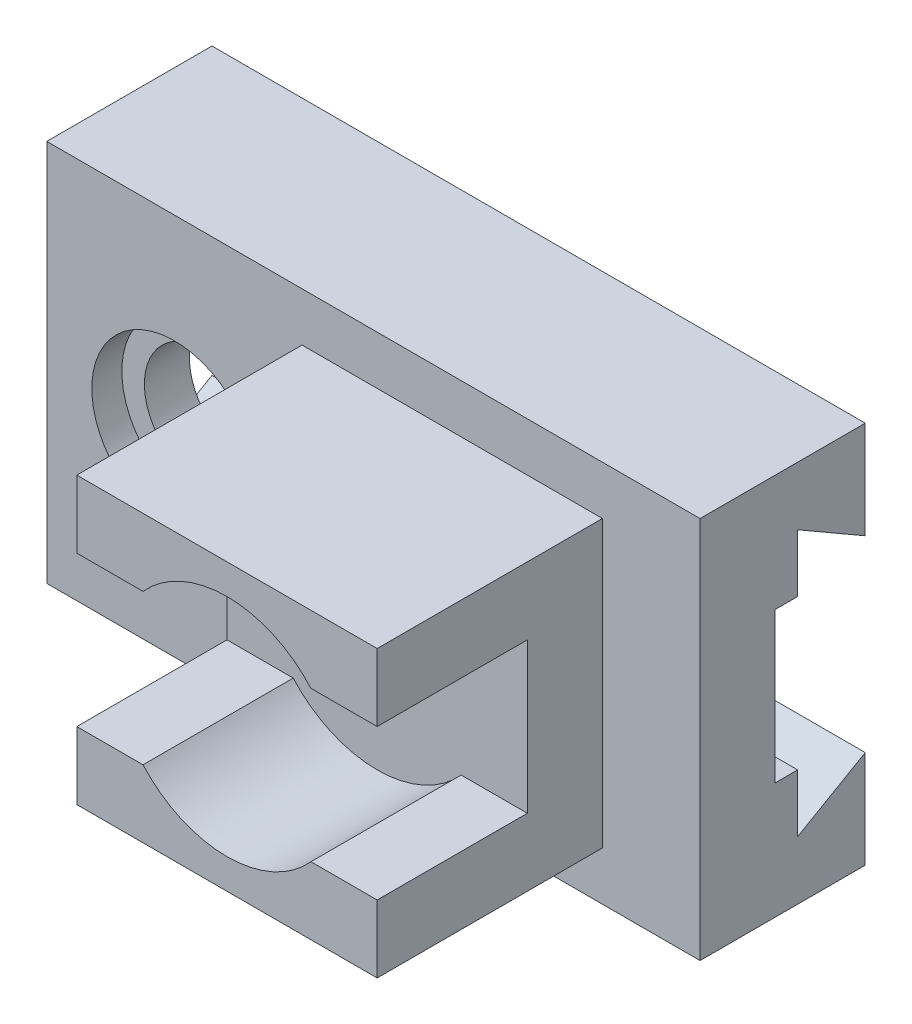
SolidWorks part; units mm, degrees
ref_plane "Front Plane" through (0, 0, 0) normal (0, 0, 1) x (1, 0, 0)
ref_plane "Top Plane" through (0, 0, 0) normal (0, 1, 0) x (1, 0, 0)
ref_plane "Right Plane" through (0, 0, 0) normal (1, 0, 0) x (0, 0, -1)
sketch "Sketch1" plane through (0, 0, 0) normal (0, 0, 1) x (1, 0, 0)
  line L0 (0, 29.2968) -> (0, -38.6677) construction
  line L1 (-48.5899, 0) -> (49.2377, 0) construction
  line L2 (-43.5, 25.491) -> (-43.5, -25.491)
  line L3 (-43.5, -25.491) -> (43.5, -25.491)
  line L4 (43.5, -25.491) -> (43.5, 25.491)
  line L5 (43.5, 25.491) -> (-43.5, 25.491)
  dimension "lengthbox" = 87
  dimension "highbox" = 50.982
extrude "base-yellow" add sketch "Sketch1" against normal blind 22
sketch "Sketch2" plane through (0, 0, 0) normal (0, 0, 1) x (1, 0, 0)
  line L0 (-55.6023, 0) -> (42.5138, 0) construction
  line L1 (-26.5, 34.8231) -> (-26.5, -37.4981) construction
  line L2 (0, 34.1505) -> (0, -37.5061) construction
  line L4 (-43.5, 25.491) -> (-43.5, -25.491) construction
  circle A0 centre (-26.5, 0) radius 11
  circle A1 centre (-26.5, 0) radius 8
  dimension "D1" = 22
  dimension "D2" = 16
  dimension "half dist" = 17
extrude "counterbor" cut sketch "Sketch2" against normal blind 4 contours A0
extrude "counterbor2" cut sketch "Sketch2<5>" against normal through all contours A1 region at (-26.5, 0, 0)
sketch "Sketch2<5>" plane through (0, 0, 0) normal (0, 0, 1) x (1, 0, 0) same geometry as "Sketch2"
ref_plane "Plane1" through (0, 0, 0) normal (0, 0, 1) x (1, 0, 0)
sketch "Sketch5" plane through (0, 0, 0) normal (0, 0, 1) x (1, 0, 0)
  line L0 (-58.6404, 0) -> (51.5993, 0) construction
  line L1 (0, 33.7865) -> (0, -36.0985) construction
  line L2 (-9.5, 19) -> (-9.5, -19)
  line L3 (-9.5, -19) -> (30.5, -19)
  line L4 (30.5, -19) -> (30.5, 19)
  line L5 (30.5, 19) -> (-9.5, 19)
  line L6 (-43.5, 25.491) -> (-43.5, -25.491) construction
  dimension "D1" = 38
  dimension "D2" = 40
  dimension "dist" = 34
extrude "base-red" add sketch "Sketch5" along normal blind 30
sketch "Sketch7" plane through (0, 0, 30) normal (0, 0, 1) x (1, 0, 0)
  line L0 (0, 34.1018) -> (0, -39.0411) construction
  line L1 (52.8604, 0) -> (-64.4204, 0) construction
  line L2 (10.5, 16.6451) -> (10.5, -21.924) construction
  line L10 (-9.5, 19) -> (-9.5, -19) construction
  line L11 (-9.5, -10) -> (30.5, -10)
  line L12 (-9.5, -10) -> (-9.5, 10)
  line L13 (-9.5, 10) -> (30.5, 10)
  line L14 (30.5, -10) -> (30.5, 10)
  line L15 (30.5, -19) -> (30.5, 19) construction
  circle A0 centre (10.5, 0) radius 15
  dimension "D2" = 30
  dimension "D1" = 20
extrude "base-purple" cut sketch "Sketch7" against normal blind 20 contours L13 A0 | L11 A0 | L12 L11 L14 L13 region at (10.5, -12.0316, 30) region at (10.5, 12.0316, 30)
sketch "Sketch8" plane through (-43.5, 0, 0) normal (-1, 0, 0) x (0, 0, 1)
  line L0 (-41.1874, 0) -> (36.1173, 0) construction
  line L1 (-10, 27.183) -> (-10, -35.8562) construction
  line L2 (0, 29.846) -> (0, -33.1932) construction
  line L3 (0, -28.0401) -> (0, 28.0401) construction
  line L4 (-10, 10) -> (-10, -10)
  line L5 (-10, -10) -> (-13, -10)
  line L6 (-10, 10) -> (-13, 10)
  line L7 (-13, -10) -> (-13, -17.6962)
  line L8 (-13, 10) -> (-13, 17.6962)
  line L9 (-13, -17.6962) -> (-22, -12.5)
  line L10 (-22, 25.491) -> (-22, -25.491) construction
  line L11 (-13, 17.6962) -> (-22, 12.5)
  line L12 (-22, 12.5) -> (-22, -12.5)
  dimension "D3" = 9
  dimension "D1" = 3
  dimension "D2" = 25
  dimension "D4" = 20
  dimension "angle" = 30
extrude "base-turkiz" cut sketch "Sketch8" against normal through all
equation "\"angle\"= 30"
equation "\"angle@Sketch8\"=\"angle\""
equation "\"dist\"= 34.00"
equation "\"half dist@Sketch2\"=\"dist\"/2"
equation "\"counterbor\" = 0"
equation "\"counterbor2\" = 0"
equation "\"highbox@Sketch1\" = \"lengthbox@Sketch1\" * 0.586"
